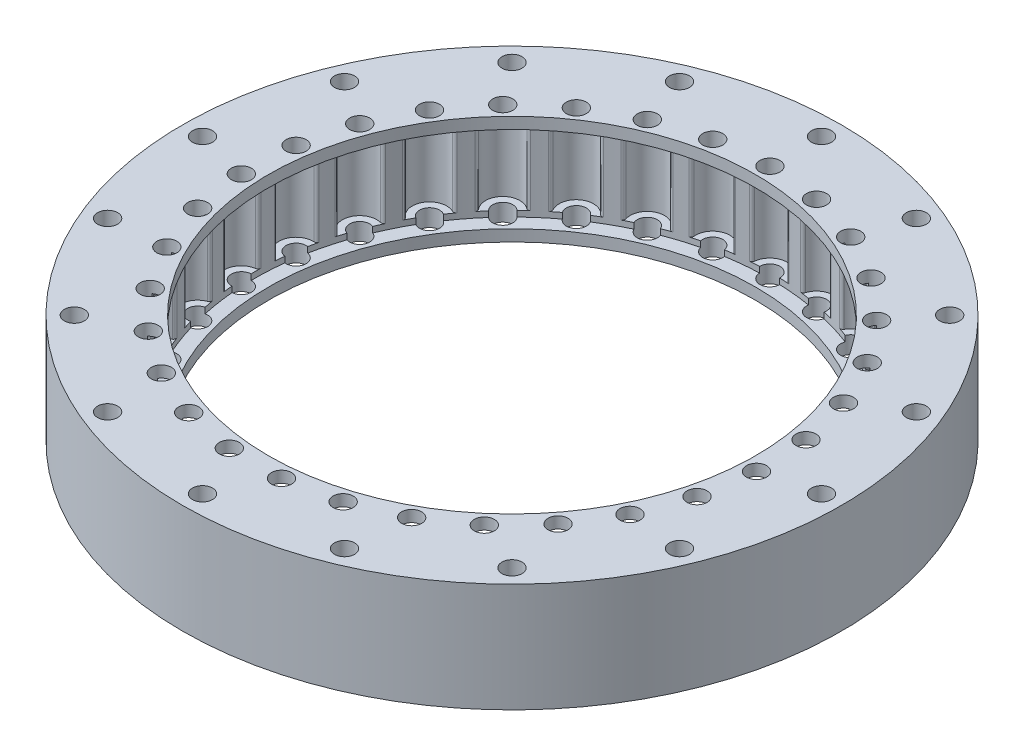
SolidWorks part; units mm, degrees
ref_plane "Front Plane" through (0, 0, 0) normal (0, 0, 1) x (1, 0, 0)
ref_plane "Top Plane" through (0, 0, 0) normal (0, 1, 0) x (1, 0, 0)
ref_plane "Right Plane" through (0, 0, 0) normal (1, 0, 0) x (0, 0, -1)
sketch "Sketch1" plane through (0, 0, 0) normal (0, 1, 0) x (1, 0, 0)
  line L0 (15.8389, 51.6249) -> (0, 0) construction
  line L1 (0, 0) -> (-4.5526, -44.7691) construction
  circle A0 centre (0, 0) radius 45
  circle A12 centre (0, 0) radius 57.5
  circle A13 centre (0, 0) radius 54 construction
  point P27 (0, 0)
  point P54 (0, 0)
  dimension "D1" = 90
  dimension "D4" = 115
  dimension "D5" = 108
  dimension "D8" = 11.25
extrude "Boss-Extrude1" add sketch "Sketch1" along normal blind 13 contours A12 region at (-55.8737, 0, 0)
sketch "Sketch2" plane through (0, 0, 0) normal (0, -1, 0) x (1, 0, 0)
  circle A0 centre (0, 0) radius 57.5
  circle A1 centre (0, 0) radius 45
extrude "Boss-Extrude2" add sketch "Sketch2" along normal blind 1
sketch "Sketch3" plane through (0, -1, 0) normal (0, -1, 0) x (1, 0, 0)
  circle A0 centre (0, 0) radius 57.5
  circle A1 centre (0, 0) radius 42.5
  dimension "D1" = 85
extrude "Boss-Extrude3" add sketch "Sketch3" along normal blind 2
sketch "Sketch5" plane through (0, 13, 0) normal (0, 1, 0) x (1, 0, 0)
  circle A0 centre (0, 45) radius 3
  circle A1 centre (0, 0) radius 45 construction
  circle A2 centre (0, 0) radius 45 construction
  dimension "D1" = 6
extrude "Cut-Extrude2" cut sketch "Sketch5" against normal blind 13
fillet "Fillet4" radius 0.5 2 edges at (2.9983, 6.5, -44.9) (-2.9983, 6.5, -44.9)
sketch "Sketch10" plane through (0, 13, 0) normal (0, 1, 0) x (1, 0, 0)
  circle A0 centre (0, 0) radius 45
  circle A1 centre (0, 0) radius 57.5
extrude "Boss-Extrude4" add sketch "Sketch10" along normal blind 1
sketch "Sketch11" plane through (0, 14, 0) normal (0, 1, 0) x (1, 0, 0)
  circle A0 centre (0, 0) radius 42.5
  circle A1 centre (0, 0) radius 57.5
extrude "Boss-Extrude5" add sketch "Sketch11" along normal blind 2
sketch "Sketch7" plane through (0, 16, 0) normal (0, 1, 0) x (1, 0, 0)
  circle A0 centre (0, 45) radius 1.75
  arc A1 (3.4425, 44.8681) -> (-3.4425, 44.8681) centre (0, 0) ccw construction
  dimension "D1" = 3.5
extrude "Cut-Extrude3" cut sketch "Sketch7" against normal blind 23
pattern_circular "CirPattern3" count 31 over 360 about axis through (0, -3, 0) along (0, 1, 0) of "Cut-Extrude2", "Fillet4", "Cut-Extrude3"
sketch "Sketch4" plane through (0, 16, 0) normal (0, 1, 0) x (1, 0, 0)
  circle A0 centre (0, 0) radius 54 construction
  circle A1 centre (0, 54) radius 1.75
  circle A2 centre (20.6649, 49.8895) radius 1.75
  circle A3 centre (38.1838, 38.1838) radius 1.75
  circle A4 centre (49.8895, 20.6649) radius 1.75
  circle A5 centre (54, 0) radius 1.75
  circle A6 centre (49.8895, -20.6649) radius 1.75
  circle A7 centre (38.1838, -38.1838) radius 1.75
  circle A8 centre (20.6649, -49.8895) radius 1.75
  circle A9 centre (0, -54) radius 1.75
  circle A10 centre (-20.6649, -49.8895) radius 1.75
  circle A11 centre (-38.1838, -38.1838) radius 1.75
  circle A12 centre (-49.8895, -20.6649) radius 1.75
  circle A13 centre (-54, 0) radius 1.75
  circle A14 centre (-49.8895, 20.6649) radius 1.75
  circle A15 centre (-38.1838, 38.1838) radius 1.75
  circle A16 centre (-20.6649, 49.8895) radius 1.75
  circle A17 centre (0, 0) radius 45 construction
  point P38 (0, 0)
  point P102 (0, 0)
  dimension "D1" = 108
  dimension "D2" = 3.5
extrude "Cut-Extrude1" cut sketch "Sketch4" against normal blind 51
